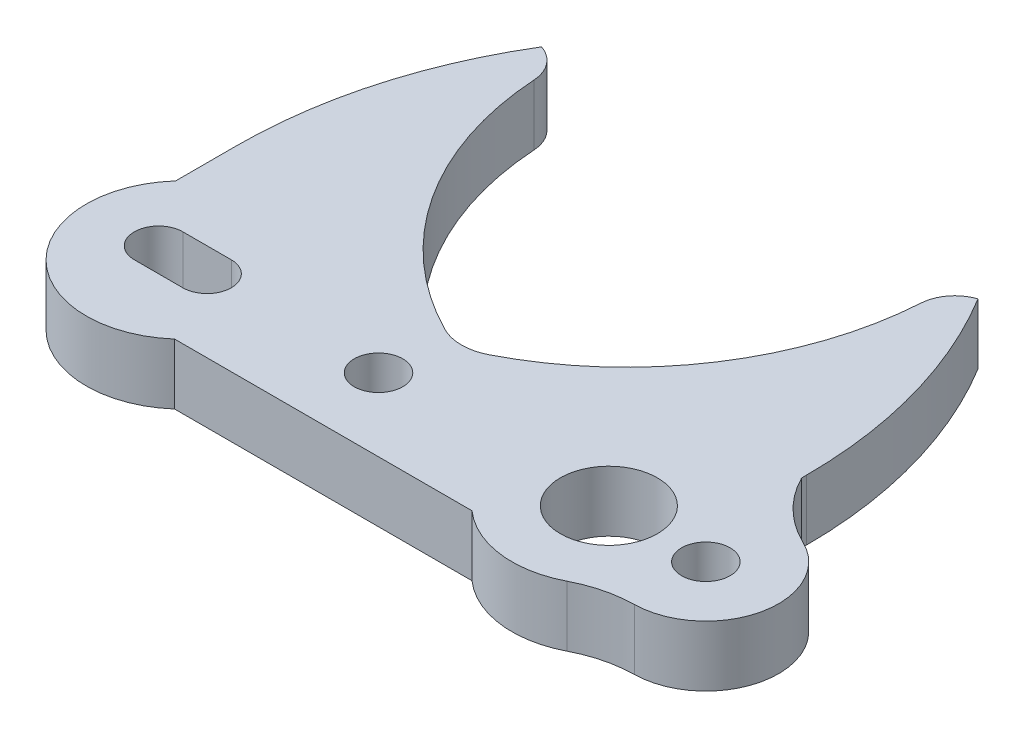
SolidWorks part; units mm, degrees
ref_plane "Front Plane" through (0, 0, 0) normal (0, 0, 1) x (1, 0, 0)
ref_plane "Top Plane" through (0, 0, 0) normal (0, 1, 0) x (1, 0, 0)
ref_plane "Right Plane" through (0, 0, 0) normal (1, 0, 0) x (0, 0, -1)
sketch "Sketch1" plane through (0, 0, 0) normal (0, 1, 0) x (1, 0, 0)
  line L0 (0, 35.9335) -> (0, 15.6254) construction
  line L1 (-16, 33.9437) -> (-16, 32.9437)
  line L2 (16, 32.9437) -> (16, 33.9437)
  line L3 (-12.2635, -2.0563) -> (12.2635, -2.0563)
  line L4 (0, -2.0563) -> (0, -28.2979) construction
  line L5 (-19.585, 5.9437) -> (-15.585, 5.9437)
  line L6 (-19.585, 1.9437) -> (-15.585, 1.9437)
  line L8 (16, 33.9437) -> (18, 33.9437)
  line L9 (17.555, 3.9437) -> (17.555, 11.4906) construction
  line L10 (-23.5148, 9.2804) -> (-23.5148, 14.2804)
  line L11 (23.5148, 13.8843) -> (23.5148, 14.2804)
  line L15 (-16, 33.9437) -> (-18, 33.9437)
  arc A0 (12.2635, -2.0563) -> (21.2217, -3.1666) centre (17.555, 3.9437) ccw
  arc A1 (-23.5148, 14.2804) -> (-18, 33.9437) centre (14.2977, 14.2804) cw
  arc A2 (-12.2635, -2.0563) -> (-23.5148, 9.2804) centre (-17.555, 3.9437) cw
  arc A3 (-16, 32.9437) -> (0, 8.9437) centre (10, 32.9437) ccw
  circle A4 centre (17.555, 3.9437) radius 4
  arc A5 (23.5148, 14.2804) -> (18, 33.9437) centre (-14.2977, 14.2804) ccw
  arc A6 (16, 32.9437) -> (0, 8.9437) centre (-10, 32.9437) cw
  circle A7 centre (25.555, 3.9437) radius 2
  arc A8 (-19.585, 5.9437) -> (-19.585, 1.9437) centre (-19.585, 3.9437) ccw
  arc A9 (-15.585, 1.9437) -> (-15.585, 5.9437) centre (-15.585, 3.9437) ccw
  circle A10 centre (-1.445, 3.9437) radius 2
  arc A11 (25.6487, -2.0556) -> (28.1388, 9.3588) centre (25.555, 3.9437) ccw
  arc A12 (28.1388, 9.3588) -> (23.5148, 13.8843) centre (32.4452, 18.3841) cw
  arc A13 (25.6487, -2.0556) -> (21.2217, -3.1666) centre (25.805, -12.0544) ccw
  point P5 (0, 3.9437)
  point P24 (-17.555, 3.9437)
  dimension "D1" = 35.11
  dimension "D3" = 8
  dimension "D2" = 19
  dimension "D4" = 10
  dimension "D5" = 10
  dimension "D6" = 37.14
extrude "Boss-Extrude1" add sketch "Sketch1" along normal blind 5
fillet "Fillet1" radius 4 1 edges at (0, 2.5, -8.9437)
fillet "Fillet2" radius 3 1 edges at (-16, 2.5, -33.9437)
fillet "Fillet3" radius 3 1 edges at (16, 2.5, -33.9437)
